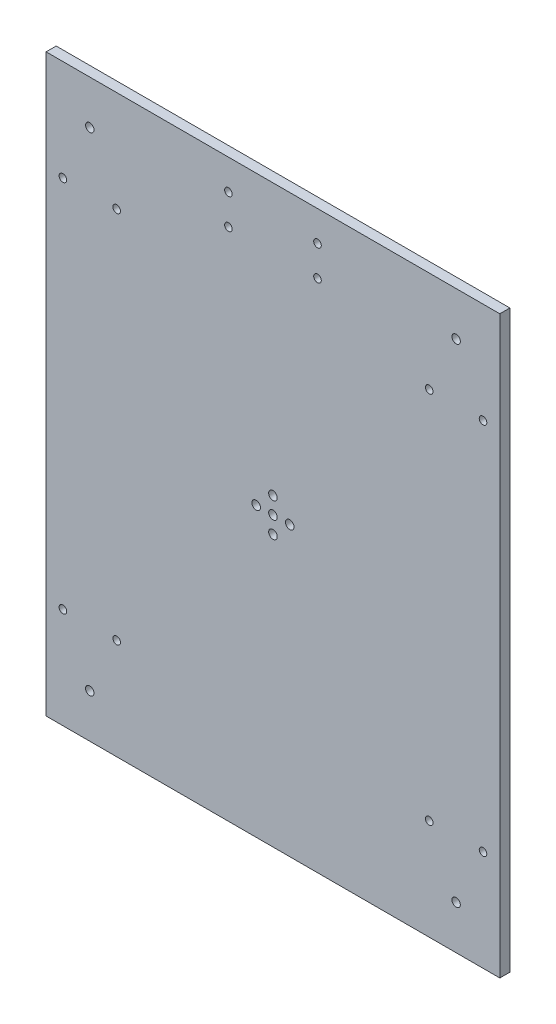
SolidWorks part; units mm, degrees
ref_plane "Спереди" through (0, 0, 0) normal (0, 0, 1) x (1, 0, 0)
ref_plane "Сверху" through (0, 0, 0) normal (0, 1, 0) x (1, 0, 0)
ref_plane "Справа" through (0, 0, 0) normal (1, 0, 0) x (0, 0, -1)
sketch "Эскиз3" plane through (0, 0, 0) normal (0, 0, 1) x (1, 0, 0)
  line L0 (0, 0) -> (0, 10) construction
  line L5 (135, -171.15) -> (-135, -171.15)
  line L6 (135, -171.15) -> (135, 171.15)
  line L7 (135, 171.15) -> (-135, 171.15)
  line L8 (-135, -171.15) -> (-135, 171.15)
  line L9 (0, 0) -> (10, 0) construction
  line L10 (0, 0) -> (0, -10) construction
  line L11 (0, 0) -> (-10, 0) construction
  circle A0 centre (0, 0) radius 2.55
  circle A1 centre (0, 10) radius 2.55
  circle A2 centre (10, 0) radius 2.55
  circle A3 centre (0, -10) radius 2.55
  circle A4 centre (-10, 0) radius 2.55
  point P0 (0, 0)
  point P5 (-135, 0)
  point P6 (0, 171.15)
  point P21 (0, 0)
  dimension "D3" = 5.1
  dimension "D4" = 5.1
  dimension "D1" = 342.3
  dimension "D2" = 270
  dimension "D5" = 10
  dimension "D6" = 4
extrude "Бобышка-Вытянуть1" add sketch "Эскиз3" along normal blind 6
sketch "Эскиз4" plane through (0, 0, 6) normal (0, 0, 1) x (1, 0, 0)
  line L0 (135, 171.15) -> (-135, 171.15) construction
  line L1 (-135, 171.15) -> (-135, -171.15) construction
  circle A0 centre (-109, 145.15) radius 2.5
  dimension "D1" = 5
  dimension "D2" = 26
  dimension "D3" = 26
extrude "Вырез-Вытянуть1" cut sketch "Эскиз4" against normal through all contours A0
pattern_linear "Линейный массив1" count 2 spacing 218 along (1, 0, 0) count 2 spacing 290.3 along (0, -1, 0) of "Вырез-Вытянуть1"
sketch "Эскиз7" plane through (0, 0, 0) normal (0, 0, -1) x (-1, 0, 0)
  line L9 (-26.5, 153.15) -> (26.5, 153.15) construction
  line L10 (-26.5, 153.15) -> (-26.5, 135.15) construction
  line L11 (-26.5, 135.15) -> (26.5, 135.15) construction
  line L16 (26.5, 153.15) -> (26.5, 135.15) construction
  line L17 (-135, 171.15) -> (135, 171.15) construction
  circle A0 centre (-26.5, 153.15) radius 2.25
  circle A1 centre (26.5, 153.15) radius 2.25
  circle A2 centre (-26.5, 135.15) radius 2.25
  circle A3 centre (26.5, 135.15) radius 2.25
  point P4 (0, 135.15)
  dimension "D4" = 4.5
  dimension "D5" = 4.5
  dimension "D6" = 4.5
  dimension "D7" = 4.5
  dimension "D1" = 53
  dimension "D2" = 18
  dimension "D3" = 18
extrude "Вырез-Вытянуть2" cut sketch "Эскиз7" against normal through all
sketch "Эскиз8" plane through (0, 0, 0) normal (0, 0, -1) x (-1, 0, 0)
  line L0 (93, 111.15) -> (125, 111.15) construction
  line L8 (135, 171.15) -> (135, -171.15) construction
  line L9 (-135, 171.15) -> (135, 171.15) construction
  circle A4 centre (93, 111.15) radius 2.25
  circle A5 centre (125, 111.15) radius 2.25
  dimension "D3" = 32
  dimension "D4" = 10
  dimension "D5" = 60
  dimension "D1" = 4.5
  dimension "D2" = 4.5
extrude "Вырез-Вытянуть3" cut sketch "Эскиз8" against normal through all
pattern_linear "Линейный массив2" count 2 spacing 222.3 along (0, -1, 0) count 2 spacing 218 along (1, 0, 0) of "Вырез-Вытянуть3"
equation "\"Ширина груза\"= 160"
equation "\"Глубина груза\"= 240"
equation "\"Высота груза\"= 160"
equation "\"Ширина ячейки\"= \"Ширина груза\" + 10"
equation "\"Глубина ячейки\"= \"Глубина груза\" + 10"
equation "\"Высота ячейки\"= \"Высота груза\" + 10 + 13"
equation "\"Колво ячеек ширина\"= 2"
equation "\"Колво ячеек высота\"= 2"
equation "\"Толщина стенки\" = \"Толщина тонких панелей\""
equation "\"Крепление дверцы\"= 5 "
equation "\"Ширина рейки\"= \"Толщина шестерни\""
equation "\"Высота рейки\"= 20"
equation "\"Высота пола\" = 2*\"Толщина тонких панелей\""
equation "\"Колво полозьев\"= 5"
equation "\"Отступ рейки\"= 20"
equation "\"Глубина каретки\"= \"Глубина ячейки\" + 30 + \"Мотор Y высота корпуса\" + 20"
equation "\"Длинна рейки\" = (\"Ширина ячейки\"+\"Толщина вертикальных стенок\"+\"Крепление дверцы\")*\"Колво ячеек ширина\"+\"Ширина ячейки выгрузки\"*\"Колво выгрузки\"+\"Толщина вертикальных стенок\"+2*\"Отступ крепления мотора фиксации\"-\"Крепление дверцы\"*\"Колво ячеек ширина\""
equation "\"Отступ шпильки\"= 26"
equation "\"Диаметр шпильки\"= 5"
equation "\"D1@Бобышка-Вытянуть1\" = \"Толщина стенки\""
equation "\"D1@Эскиз4\"= \"Диаметр шпильки\""
equation "\"D2@Эскиз4\"=\"Отступ шпильки\""
equation "\"D3@Эскиз4\"= \"Отступ шпильки\""
equation "\"D2@Эскиз3\"=\"Ширина ячейки\" + \"Ширина пластины\" * 2"
equation "\"D1@Эскиз3\"=\"Глубина каретки\" "
equation "\"D3@Линейный массив1\"=\"Ширина ячейки\"  +\"Ширина пластины\" *2 - \"Отступ шпильки\" * 2"
equation "\"D4@Линейный массив1\"=\"Глубина каретки\" + \"Ширина рейки\" * 2 - \"Отступ шпильки\" * 2 - \"Ширина рейки\" * 2"
equation "\"Длинна шпильки\" = (\"Высота ячейки\"+\"Толщина горизонтальных плит\"+\"Высота пола\")*\"Колво ячеек высота\"+2*(\"Толщина горизонтальных плит\"+\"Отступ рейки\")"
equation "\"Ширина пластины\"= 50  "
equation "\"Высота зона выгрузки\"= \"Высота ячейки\" * 2 + \"Толщина стенки\" * 2"
equation "\"Колво выгрузки\"= 1"
equation "\"Отступ крепления мотора фиксации\" = (\"Ширина пластины\"+20-\"Толщина вертикальных стенок\")/2"
equation "\"Мотор X ширина корпуса\"= 42.3"
equation "\"Мотор X высота корпуса\"= 42.3"
equation "\"Мотор X длина корпуса\"= 40"
equation "\"Мотор X вылет вала\"= 19.8"
equation "\"Мотор Y ширина корпуса\"= 42.3"
equation "\"Мотор Y высота корпуса\"= 42.3"
equation "\"Мотор Y длина корпуса\"= 48"
equation "\"Мотор Y вылет вала\"= 30"
equation "\"Мотор Z ширина корпуса\"= 42"
equation "\"Мотор Z высота корпуса\"= 42"
equation "\"Мотор Z длина корпуса\"= 40"
equation "\"Мотор Z вылет вала\"= 23"
equation "\"Мотор диаметр вала ПРЕДВ\"= 5"
equation "\"Мотор шаг крепления ПРЕДВ\"= 31"
equation "\"Мотор диаметр отверстий ПРЕДВ\"= 3"
equation "\"Мотор глубина отверстий ПРЕДВ\"= 4.5"
equation "\"Мотор диаметр буртика ПРЕДВ\"= 22"
equation "\"Мотор высота буртика ПРЕДВ\"= 2"
equation "\"Мотор диаметр шкива ПРЕДВ\"= 16"
equation "\"Мотор длина шкива ПРЕДВ\"= 12"
equation "\"Мотор отступ шкива ПРЕДВ\"= 5"
equation "\"Мотор X шаг градусов\"= 1.8"
equation "\"Мотор Y шаг градусов\"= 1.8"
equation "\"Мотор Z шаг градусов\"= 1.8"
equation "\"Мотор Y диаметр ротора\"= 25.78"
equation "\"Толщина шестерни\"= 10"
equation "\"Ширина ячейки выгрузки\" = \"Ширина ячейки\"+\"Толщина вертикальных стенок\"+2*\"Отступ крепления мотора фиксации\""
equation "\"D3@Линейный массив2\" = \"Глубина каретки\"-120"
equation "\"D4@Линейный массив2\" = \"Ширина ячейки\"+2*\"Ширина пластины\"-2*\"Отступ шпильки\""
equation "\"Толщина тонких панелей\" = 6"
equation "\"Толщина вертикальных стенок\" = 6"
equation "\"Толщина горизонтальных плит\" = 6"
equation "\"Базовая высота корпуса\"= (\"Высота ячейки\"+\"Толщина тонких панелей\"+\"Высота пола\")*\"Колво ячеек высота\"+6*\"Толщина тонких панелей\"+\"Мотор X ширина корпуса\"+\"Мотор Y ширина корпуса\"+75"
equation "\"Высота корпуса\"= (\"Высота ячейки\"+\"Толщина горизонтальных плит\"+\"Высота пола\")*\"Колво ячеек высота\"+2*\"Толщина горизонтальных плит\"+4*\"Толщина тонких панелей\"+\"Мотор X ширина корпуса\"+\"Мотор Y ширина корпуса\"+75"
equation "\"Смещение центра корпуса\"= (\"Высота корпуса\"-\"Базовая высота корпуса\")/2-(\"Толщина горизонтальных плит\"-\"Толщина тонких панелей\")"
equation "\"Отметка пола\"= -\"Базовая высота корпуса\"/2+\"Толщина тонких панелей\""
equation "\"Отметка потолка\"= \"Отметка пола\"+\"Высота корпуса\"-2*\"Толщина горизонтальных плит\""
equation "\"Отметка верхней полки\"= \"Отметка потолка\"-(28+\"Толщина тонких панелей\")-\"Высота ячейки\"-\"Высота пола\""
equation "\"Отметка нижней полки\"= \"Отметка верхней полки\"-\"Высота ячейки\"-\"Высота пола\"-\"Толщина горизонтальных плит\""
